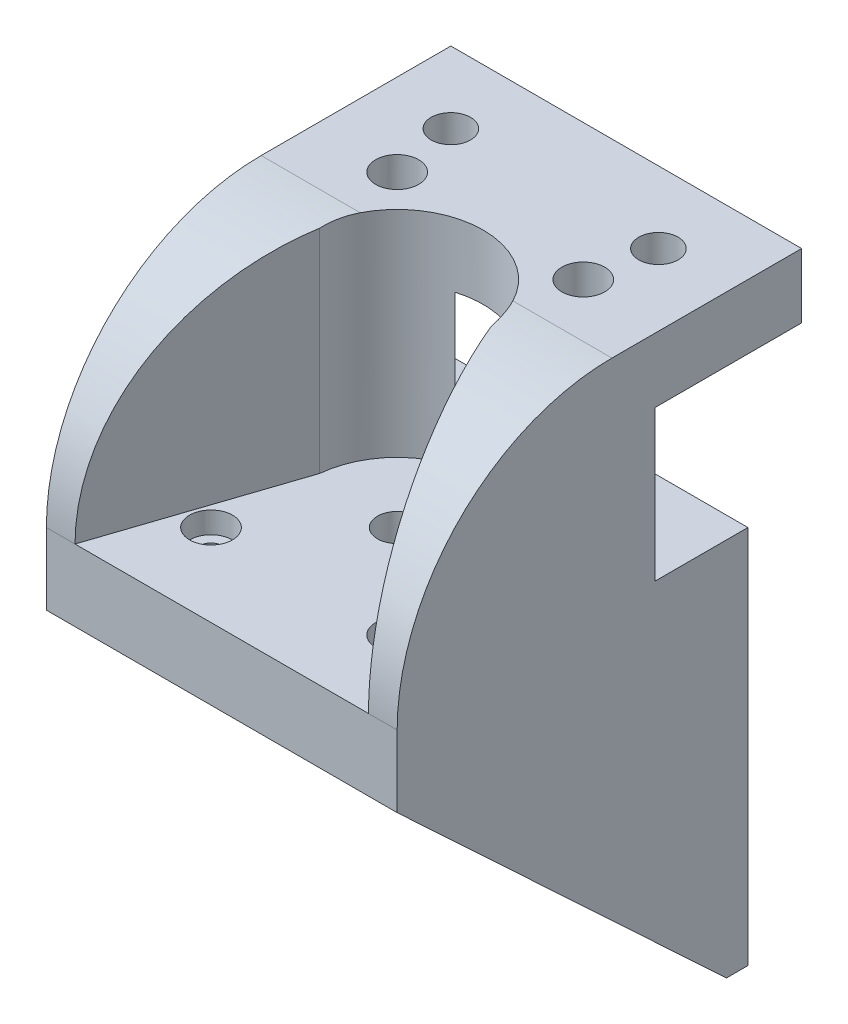
SolidWorks part; units mm, degrees
ref_plane "Front" through (0, 0, 0) normal (0, 0, 1) x (1, 0, 0)
ref_plane "Top" through (0, 0, 0) normal (0, 1, 0) x (1, 0, 0)
ref_plane "Right" through (0, 0, 0) normal (1, 0, 0) x (0, 0, -1)
sketch "Sketch1" plane through (0, 0, 0) normal (0, 1, 0) x (1, 0, 0)
  line L0 (0, 24.5) -> (0, -24.5) construction
  line L1 (-24.5, 24.5) -> (24.5, 24.5)
  line L2 (-24.5, 24.5) -> (-24.5, -24.5)
  line L3 (-24.5, -24.5) -> (24.5, -24.5)
  line L4 (24.5, 24.5) -> (24.5, -24.5)
  line L5 (24.5, 0) -> (-24.5, 0) construction
  line L6 (0, -50) -> (0, 50) construction
  line L7 (-50, 0) -> (50, 0) construction
  circle A0 centre (0, 0) radius 2.75
  point P4 (0, 24.5)
  dimension "D1" = 49
  dimension "D2" = 49
extrude "Boss-Extrude1" add sketch "Sketch1" along normal blind 53
sketch "Sketch2" plane through (0, 0, 0) normal (0, -1, 0) x (1, 0, 0)
  line L0 (24.5, -24.5) -> (-24.5, -24.5) construction
  line L1 (-22, -22) -> (22, -22)
  line L2 (-22, -22) -> (-22, 22)
  line L3 (-22, 22) -> (22, 22)
  line L4 (22, -22) -> (22, 22)
  line L5 (-24.5, -24.5) -> (-24.5, 24.5) construction
  dimension "D1" = 44
  dimension "D2" = 44
  dimension "D3" = 2.5
  dimension "D4" = 2.5
extrude "Cut-Extrude1" cut sketch "Sketch2" against normal blind 47
sketch "Sketch3" plane through (0, 47, 0) normal (0, -1, 0) x (1, 0, 0)
  circle A0 centre (0, 0) radius 12
  dimension "D1" = 24
extrude "Cut-Extrude2" cut sketch "Sketch3" against normal blind 2
sketch "Sketch4" plane through (0, 53, 0) normal (0, 1, 0) x (1, 0, 0)
  line L0 (24.5, -24.5) -> (24.5, 24.5) construction
  line L1 (-24.5, -24.5) -> (24.5, -24.5) construction
  circle A0 centre (-13, -13) radius 1.6
  circle A1 centre (-13, 13) radius 1.6
  circle A2 centre (13, 13) radius 1.6
  circle A3 centre (13, -13) radius 1.6
  dimension "D1" = 3.2
  dimension "D2" = 3.2
  dimension "D3" = 3.2
  dimension "D4" = 3.2
  dimension "D5" = 26
  dimension "D6" = 26
  dimension "D7" = 11.5
  dimension "D8" = 11.5
extrude "Cut-Extrude3" cut sketch "Sketch4" against normal blind 10
sketch "Sketch5" plane through (0, 53, 0) normal (0, 1, 0) x (1, 0, 0)
  line L0 (24.5, 24.5) -> (-24.5, 24.5) construction
  line L1 (-20.5, -24.5) -> (-11.947, 1.1271)
  line L2 (11.947, 1.1271) -> (-11.947, 1.1271) construction
  line L3 (24.5, 32) -> (-24.5, 32)
  line L5 (-24.5, -24.5) -> (24.5, -24.5) construction
  line L6 (-20.5, -24.5) -> (-24.5, -24.5)
  line L7 (-24.5, -24.5) -> (-24.5, 32)
  line L8 (20.5, -24.5) -> (24.5, -24.5)
  line L9 (24.5, -24.5) -> (24.5, 32)
  line L10 (24.5, -24.5) -> (24.5, 24.5) construction
  line L11 (11.947, 1.1271) -> (20.5, -24.5)
  arc A0 (0, 12) -> (11.947, 1.1271) centre (0, 0) cw
  arc A1 (0, 12) -> (-11.947, 1.1271) centre (0, 0) ccw
  dimension "D2" = 7.5
  dimension "D3" = 4
  dimension "D4" = 4
  dimension "D1" = 12.5
extrude "Boss-Extrude2" add sketch "Sketch5" along normal blind 30
sketch "Sketch7" plane through (-24.5, 0, 0) normal (-1, 0, 0) x (0, 0, 1)
  line L1 (-32, 53) -> (-11.5, 53)
  line L2 (-32, 53) -> (-32, 74)
  line L3 (-32, 74) -> (-11.5, 74)
  line L4 (-11.5, 53) -> (-11.5, 74)
  dimension "D1" = 21
  dimension "D2" = 20.5
extrude "Cut-Extrude6" cut sketch "Sketch7" against normal blind 59
sketch "Sketch9" plane through (0, 53, 0) normal (0, 1, 0) x (1, 0, 0)
  circle A0 centre (-13, 13) radius 3
  circle A1 centre (13, 13) radius 3
  circle A2 centre (-13, -13) radius 3
  circle A3 centre (13, -13) radius 3
  dimension "D1" = 6
  dimension "D2" = 6
  dimension "D3" = 6
  dimension "D4" = 6
extrude "Cut-Extrude7" cut sketch "Sketch9" along normal blind 59
sketch "Sketch10" plane through (0, 74, 0) normal (0, -1, 0) x (1, 0, 0)
  line L0 (14.5, -22) -> (-14.5, -22) construction
  line L1 (24.5, -32) -> (-24.5, -32) construction
  line L3 (24.5, -11.5) -> (24.5, -32) construction
  line L4 (-24.5, -11.5) -> (-24.5, -32) construction
  line L5 (24.5, -32) -> (-24.5, -32) construction
  circle A0 centre (14.5, -22) radius 2.75
  circle A1 centre (-14.5, -22) radius 2.75
  dimension "D1" = 5.5
  dimension "D2" = 5.5
  dimension "D3" = 10
  dimension "D4" = 10
  dimension "D5" = 10
extrude "Cut-Extrude8" cut sketch "Sketch10" against normal blind 59
fillet "Fillet1" radius 30 1 edges at (22.5, 83, 24.5)
fillet "Fillet2" radius 30 1 edges at (-22.5, 83, 24.5)
sketch "Sketch11" plane through (-24.5, 0, 0) normal (-1, 0, 0) x (0, 0, 1)
  line L0 (24.5, 0) -> (-21.5, 0)
  line L1 (-24.5, 0) -> (24.5, 0) construction
  line L2 (-21.5, 0) -> (24.5, 43)
  line L3 (24.5, 53) -> (24.5, 0) construction
  line L4 (24.5, 43) -> (24.5, 0)
  dimension "D1" = 3
  dimension "D2" = 10
extrude "Cut-Extrude9" cut sketch "Sketch11" against normal blind 59
sketch "Sketch12" plane through (0, 53, 0) normal (0, 1, 0) x (1, 0, 0)
  circle A0 centre (-13, 13) radius 3
  circle A1 centre (13, -13) radius 3
  circle A2 centre (-13, -13) radius 3
  circle A3 centre (13, 13) radius 3
  dimension "D1" = 6
  dimension "D3" = 6
  dimension "D4" = 6
  dimension "D2" = 6
extrude "Cut-Extrude10" cut sketch "Sketch12" against normal blind 3
equation "\"D2@Sketch1\"=\"D1@Sketch1\""
equation "\"D2@Sketch2\"=\"D1@Sketch2\""
equation "\"D3@Sketch2\"=(\"D1@Sketch1\"-\"D1@Sketch2\")/2"
equation "\"D4@Sketch2\"=\"D3@Sketch2\""
equation "\"D2@Sketch4\"=\"D1@Sketch4\""
equation "\"D3@Sketch4\"=\"D1@Sketch4\""
equation "\"D4@Sketch4\"=\"D1@Sketch4\""
equation "\"D6@Sketch4\"=\"D5@Sketch4\""
equation "\"D7@Sketch4\"=(49-\"D5@Sketch4\")/2"
equation "\"D8@Sketch4\"=(49-\"D6@Sketch4\")/2"
equation "\"D1@Sketch5\"=\"D2@Sketch1\"/2-\"D1@Sketch3\"/2"
equation "\"D4@Sketch5\"=\"D3@Sketch5\""
equation "\"D2@Sketch5\"= 20 - \"D1@Sketch5\""
equation "\"D3@Sketch9\"=\"D4@Sketch9\""
equation "\"D2@Sketch9\"=\"D4@Sketch9\""
equation "\"D1@Sketch9\"=\"D4@Sketch9\""
equation "\"D2@Sketch10\"=\"D1@Sketch10\""
equation "\"D4@Sketch10\"=\"D3@Sketch10\""
equation "\"D2@Sketch12\"=\"D1@Sketch12\""
equation "\"D3@Sketch12\"=\"D1@Sketch12\""
equation "\"D4@Sketch12\"=\"D1@Sketch12\""
